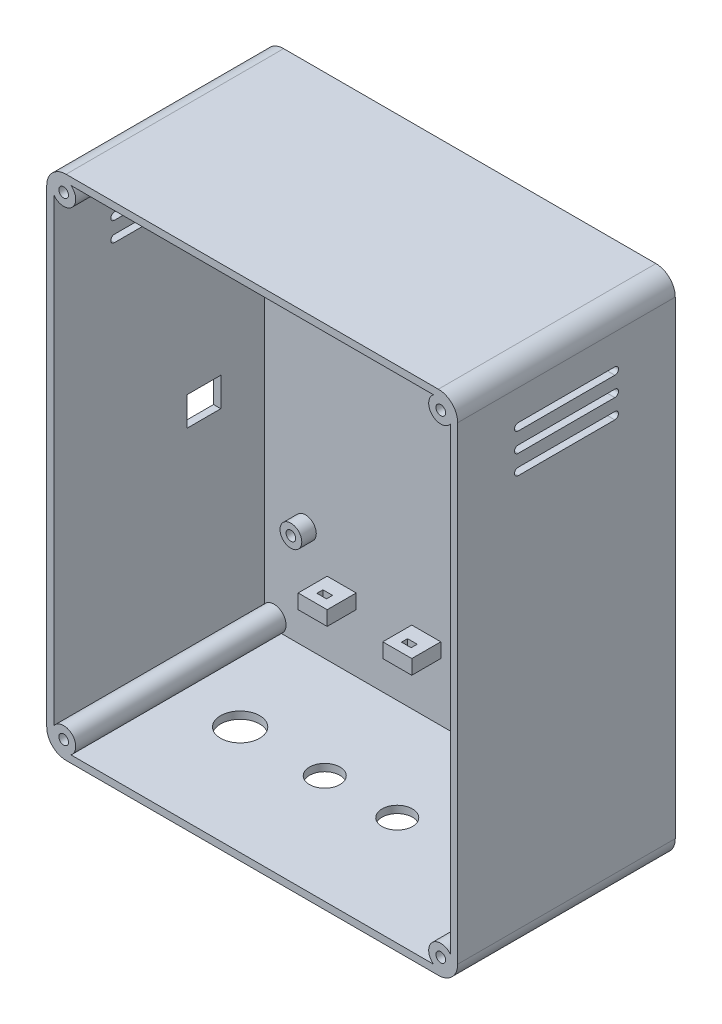
SolidWorks part; units mm, degrees
ref_plane "Front Plane" through (0, 0, 0) normal (0, 0, 1) x (1, 0, 0)
ref_plane "Top Plane" through (0, 0, 0) normal (0, 1, 0) x (1, 0, 0)
ref_plane "Right Plane" through (0, 0, 0) normal (1, 0, 0) x (0, 0, -1)
sketch "Sketch1" plane through (0, 0, 0) normal (0, 0, 1) x (1, 0, 0)
  line L0 (-77, 0) -> (77, 0)
  line L1 (85, 8) -> (85, 202)
  line L2 (77, 210) -> (-77, 210)
  line L3 (-85, 202) -> (-85, 8)
  arc A0 (-85, 8) -> (-77, 0) centre (-77, 8) ccw
  arc A1 (77, 0) -> (85, 8) centre (77, 8) ccw
  arc A2 (85, 202) -> (77, 210) centre (77, 202) ccw
  arc A3 (-77, 210) -> (-85, 202) centre (-77, 202) ccw
extrude "Block" add sketch "Sketch1" along normal blind 90
shell "Shell1" thickness 3 removed face at (0, 105, 90)
sketch "Sketch2" plane through (0, 0, 0) normal (0, 0, 1) x (1, 0, 0)
  circle A0 centre (-78, 7) radius 5
  circle A1 centre (78, 7) radius 5
  circle A2 centre (-78, 203) radius 5
  circle A3 centre (78, 203) radius 5
extrude "Corner columns" add sketch "Sketch2" along normal blind 90
ref_plane "P1_Front_90" through (0, 0, 90) normal (0, 0, 1) x (1, 0, 0)
sketch "Sketch3" plane through (0, 0, 90) normal (0, 0, 1) x (1, 0, 0)
  circle A0 centre (-78, 7) radius 2
  circle A1 centre (78, 7) radius 2
  circle A2 centre (-78, 203) radius 2
  circle A3 centre (78, 203) radius 2
extrude "Front panel insert holes" cut sketch "Sketch3" against normal blind 7
ref_plane "P2_Front_3" through (0, 0, 3) normal (0, 0, 1) x (1, 0, 0)
sketch "Sketch4" plane through (0, 0, 3) normal (0, 0, 1) x (1, 0, 0)
  circle A0 centre (-65, 46) radius 4.5
  circle A1 centre (65, 46) radius 4.5
  circle A2 centre (-65, 190) radius 4.5
  circle A3 centre (65, 190) radius 4.5
extrude "Plate bosses" add sketch "Sketch4" along normal blind 6
ref_plane "P3_Front_9" through (0, 0, 9) normal (0, 0, 1) x (1, 0, 0)
sketch "Sketch5" plane through (0, 0, 9) normal (0, 0, 1) x (1, 0, 0)
  circle A0 centre (-65, 46) radius 2
  circle A1 centre (65, 46) radius 2
  circle A2 centre (-65, 190) radius 2
  circle A3 centre (65, 190) radius 2
extrude "Plate insert holes" cut sketch "Sketch5" against normal blind 7
sketch "Sketch6" plane through (0, 0, 0) normal (0, 1, 0) x (1, 0, 0)
  circle A0 centre (-50, -45) radius 8.1
  circle A1 centre (-15, -45) radius 6.3
  circle A2 centre (15, -45) radius 6.3
  circle A3 centre (50, -45) radius 6.3
extrude "Cable gland holes" cut sketch "Sketch6" along normal blind 4
sketch "Sketch7" plane through (0, 0, 3) normal (0, 0, 1) x (1, 0, 0)
  line L1 (-56, 27) -> (-44, 27)
  line L2 (-56, 27) -> (-56, 33)
  line L3 (-56, 33) -> (-44, 33)
  line L4 (-44, 27) -> (-44, 33)
  line L5 (-56, 27) -> (-44, 33) construction
  line L6 (-56, 33) -> (-44, 27) construction
  line L7 (-21, 27) -> (-9, 27)
  line L8 (-21, 27) -> (-21, 33)
  line L9 (-21, 33) -> (-9, 33)
  line L10 (-9, 27) -> (-9, 33)
  line L11 (-21, 27) -> (-9, 33) construction
  line L12 (-21, 33) -> (-9, 27) construction
  line L13 (9, 27) -> (21, 27)
  line L14 (9, 27) -> (9, 33)
  line L15 (9, 33) -> (21, 33)
  line L16 (21, 27) -> (21, 33)
  line L17 (9, 27) -> (21, 33) construction
  line L18 (9, 33) -> (21, 27) construction
  line L19 (44, 27) -> (56, 27)
  line L20 (44, 27) -> (44, 33)
  line L21 (44, 33) -> (56, 33)
  line L22 (56, 27) -> (56, 33)
  line L23 (44, 27) -> (56, 33) construction
  line L24 (44, 33) -> (56, 27) construction
  point P0 (-50, 30)
  point P5 (-15, 30)
  point P10 (15, 30)
  point P15 (50, 30)
extrude "Cable tie bars" add sketch "Sketch7" along normal blind 12
ref_plane "P4_Top_26.99" through (0, 26.99, 0) normal (0, 1, 0) x (1, 0, 0)
sketch "Sketch8" plane through (0, 26.99, 0) normal (0, 1, 0) x (1, 0, 0)
  line L1 (-52, -11.25) -> (-48, -11.25)
  line L2 (-52, -11.25) -> (-52, -8.75)
  line L3 (-52, -8.75) -> (-48, -8.75)
  line L4 (-48, -11.25) -> (-48, -8.75)
  line L5 (-52, -11.25) -> (-48, -8.75) construction
  line L6 (-52, -8.75) -> (-48, -11.25) construction
  line L7 (-17, -11.25) -> (-13, -11.25)
  line L8 (-17, -11.25) -> (-17, -8.75)
  line L9 (-17, -8.75) -> (-13, -8.75)
  line L10 (-13, -11.25) -> (-13, -8.75)
  line L11 (-17, -11.25) -> (-13, -8.75) construction
  line L12 (-17, -8.75) -> (-13, -11.25) construction
  line L13 (13, -11.25) -> (17, -11.25)
  line L14 (13, -11.25) -> (13, -8.75)
  line L15 (13, -8.75) -> (17, -8.75)
  line L16 (17, -11.25) -> (17, -8.75)
  line L17 (13, -11.25) -> (17, -8.75) construction
  line L18 (13, -8.75) -> (17, -11.25) construction
  line L19 (48, -11.25) -> (52, -11.25)
  line L20 (48, -11.25) -> (48, -8.75)
  line L21 (48, -8.75) -> (52, -8.75)
  line L22 (52, -11.25) -> (52, -8.75)
  line L23 (48, -11.25) -> (52, -8.75) construction
  line L24 (48, -8.75) -> (52, -11.25) construction
  point P0 (-50, -10)
  point P5 (-15, -10)
  point P10 (15, -10)
  point P15 (50, -10)
extrude "Cable tie slots" cut sketch "Sketch8" along normal blind 6.02
ref_plane "P5_Right_-85" through (-85, 0, 0) normal (1, 0, 0) x (0, 0, -1)
sketch "Sketch9" plane through (-85, 0, 0) normal (1, 0, 0) x (0, 0, -1)
  line L1 (-35, 89) -> (-21, 89)
  line L2 (-35, 89) -> (-35, 101)
  line L3 (-35, 101) -> (-21, 101)
  line L4 (-21, 89) -> (-21, 101)
  line L5 (-35, 89) -> (-21, 101) construction
  line L6 (-35, 101) -> (-21, 89) construction
  point P0 (-28, 95)
extrude "USB access" cut sketch "Sketch9" along normal blind 4
ref_plane "P6_Right_-85" through (-85, 0, 0) normal (1, 0, 0) x (0, 0, -1)
sketch "Sketch10" plane through (-85, 0, 0) normal (1, 0, 0) x (0, 0, -1)
  line L0 (-25, 172) -> (-65, 172) construction
  line L1 (-25, 170.5) -> (-65, 170.5)
  line L2 (-25, 173.5) -> (-65, 173.5)
  line L3 (-25, 180) -> (-65, 180) construction
  line L4 (-25, 178.5) -> (-65, 178.5)
  line L5 (-25, 181.5) -> (-65, 181.5)
  line L6 (-25, 188) -> (-65, 188) construction
  line L7 (-25, 186.5) -> (-65, 186.5)
  line L8 (-25, 189.5) -> (-65, 189.5)
  arc A0 (-25, 170.5) -> (-25, 173.5) centre (-25, 172) ccw
  arc A1 (-65, 173.5) -> (-65, 170.5) centre (-65, 172) ccw
  arc A2 (-25, 178.5) -> (-25, 181.5) centre (-25, 180) ccw
  arc A3 (-65, 181.5) -> (-65, 178.5) centre (-65, 180) ccw
  arc A4 (-25, 186.5) -> (-25, 189.5) centre (-25, 188) ccw
  arc A5 (-65, 189.5) -> (-65, 186.5) centre (-65, 188) ccw
  point P2 (-45, 172)
  point P7 (-45, 180)
  point P14 (-45, 188)
  point P21 (0, 0)
extrude "Vents left" cut sketch "Sketch10" along normal blind 4
ref_plane "P7_Right_85" through (85, 0, 0) normal (1, 0, 0) x (0, 0, -1)
sketch "Sketch11" plane through (85, 0, 0) normal (1, 0, 0) x (0, 0, -1)
  line L0 (-25, 172) -> (-65, 172) construction
  line L1 (-25, 170.5) -> (-65, 170.5)
  line L2 (-25, 173.5) -> (-65, 173.5)
  line L3 (-25, 180) -> (-65, 180) construction
  line L4 (-25, 178.5) -> (-65, 178.5)
  line L5 (-25, 181.5) -> (-65, 181.5)
  line L6 (-25, 188) -> (-65, 188) construction
  line L7 (-25, 186.5) -> (-65, 186.5)
  line L8 (-25, 189.5) -> (-65, 189.5)
  arc A0 (-25, 170.5) -> (-25, 173.5) centre (-25, 172) ccw
  arc A1 (-65, 173.5) -> (-65, 170.5) centre (-65, 172) ccw
  arc A2 (-25, 178.5) -> (-25, 181.5) centre (-25, 180) ccw
  arc A3 (-65, 181.5) -> (-65, 178.5) centre (-65, 180) ccw
  arc A4 (-25, 186.5) -> (-25, 189.5) centre (-25, 188) ccw
  arc A5 (-65, 189.5) -> (-65, 186.5) centre (-65, 188) ccw
  point P2 (-45, 172)
  point P7 (-45, 180)
  point P14 (-45, 188)
  point P21 (0, 0)
extrude "Vents right" cut sketch "Sketch11" against normal blind 4
sketch "Sketch12" plane through (0, 0, 0) normal (0, 0, 1) x (1, 0, 0)
  circle A0 centre (-45, 165) radius 4.75
  circle A1 centre (45, 165) radius 4.75
extrude "Keyhole heads" cut sketch "Sketch12" along normal blind 4
sketch "Sketch13" plane through (0, 0, 0) normal (0, 0, 1) x (1, 0, 0)
  line L0 (-45, 165) -> (-45, 176) construction
  line L1 (-47.4, 165) -> (-47.4, 176)
  line L2 (-42.6, 165) -> (-42.6, 176)
  line L3 (45, 165) -> (45, 176) construction
  line L4 (42.6, 165) -> (42.6, 176)
  line L5 (47.4, 165) -> (47.4, 176)
  arc A0 (-47.4, 165) -> (-42.6, 165) centre (-45, 165) ccw
  arc A1 (-42.6, 176) -> (-47.4, 176) centre (-45, 176) ccw
  arc A2 (42.6, 165) -> (47.4, 165) centre (45, 165) ccw
  arc A3 (47.4, 176) -> (42.6, 176) centre (45, 176) ccw
  point P2 (-45, 170.5)
  point P7 (45, 170.5)
  point P14 (0, 0)
extrude "Keyhole slots" cut sketch "Sketch13" along normal blind 4
